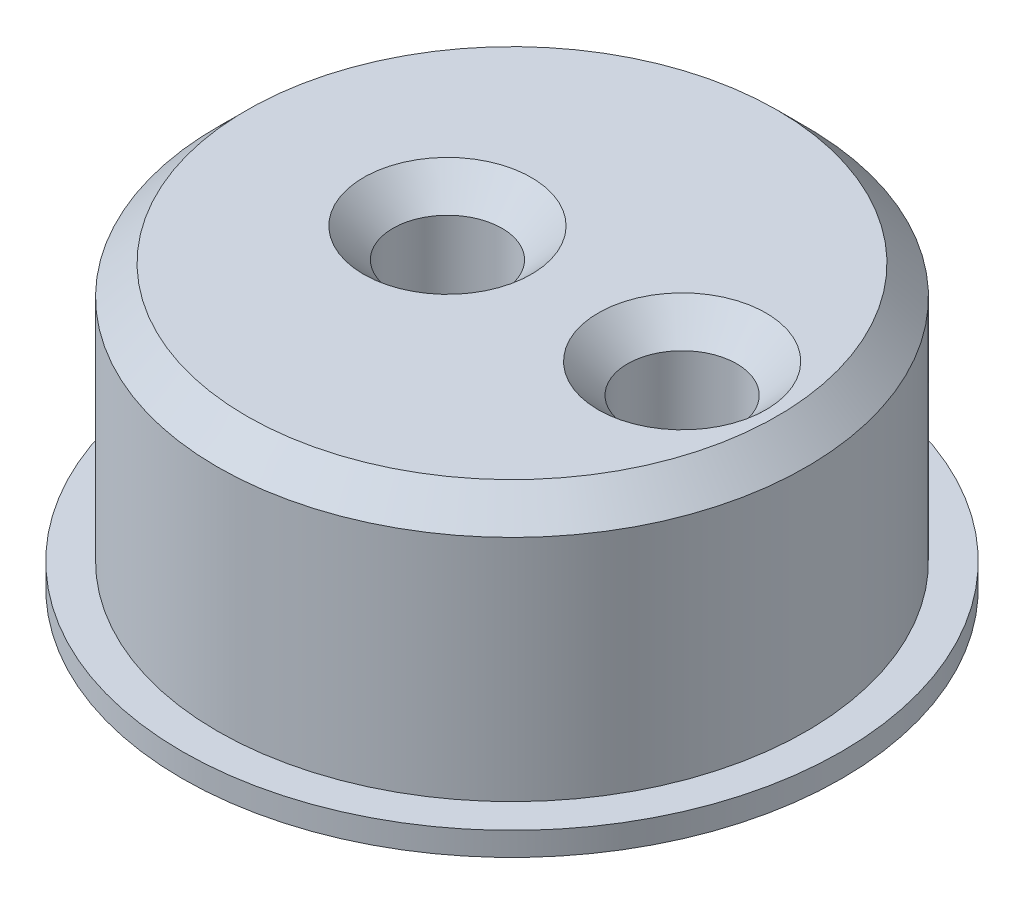
SolidWorks part; units mm, degrees
ref_plane "前视基准面" through (0, 0, 0) normal (0, 0, 1) x (1, 0, 0)
ref_plane "上视基准面" through (0, 0, 0) normal (0, 1, 0) x (1, 0, 0)
ref_plane "右视基准面" through (0, 0, 0) normal (1, 0, 0) x (0, 0, -1)
other "Configuration Table"
sketch "草图1" plane through (0, 0, 0) normal (0, 1, 0) x (1, 0, 0)
  line L0 (0.9, 6.4178) -> (0.9, -6.4114) construction
  line L1 (-5.7349, 0) -> (5.8104, 0) construction
  circle A0 centre (0, 0) radius 5.02
  circle A1 centre (2.9, 0) radius 0.93
  circle A2 centre (-1.1, 0) radius 0.93
  dimension "D1" = 10.04
  dimension "D3" = 4
  dimension "D4" = 1.86
  dimension "D2" = 0.9
extrude "凸台-拉伸1" add sketch "草图1" along normal blind 4.4
sketch "草图3" plane through (0, 0, 0) normal (0, -1, 0) x (1, 0, 0)
  circle A0 centre (2.9, 0) radius 0.93 construction
  circle A1 centre (0, 0) radius 5.02 construction
  circle A3 centre (-1.1, 0) radius 0.93 construction
  circle A4 centre (2.9, 0) radius 0.93
  circle A5 centre (-1.1, 0) radius 0.93
  circle A6 centre (0, 0) radius 5.02 construction
  circle A7 centre (0, 0) radius 5.62
  dimension "D1" = 0.6
extrude "凸台-拉伸2" add sketch "草图3" along normal blind 0.4
chamfer "倒角1" distance 0.5 angle 45 5 edges at (0, 4.4, 5.02) (-1.1, 4.4, -0.93) (2.9, 4.4, 0.93) (-1.1, -0.4, -0.93) (2.9, -0.4, -0.93)
ref_axis "基准轴1" through (0, 3.9, 0) along (0, -1, 0)
sketch "草图2" plane through (0, 0, 0) normal (0, 1, 0) x (1, 0, 0)
  line L0 (-5.9042, 0) -> (6.2358, 0) construction
